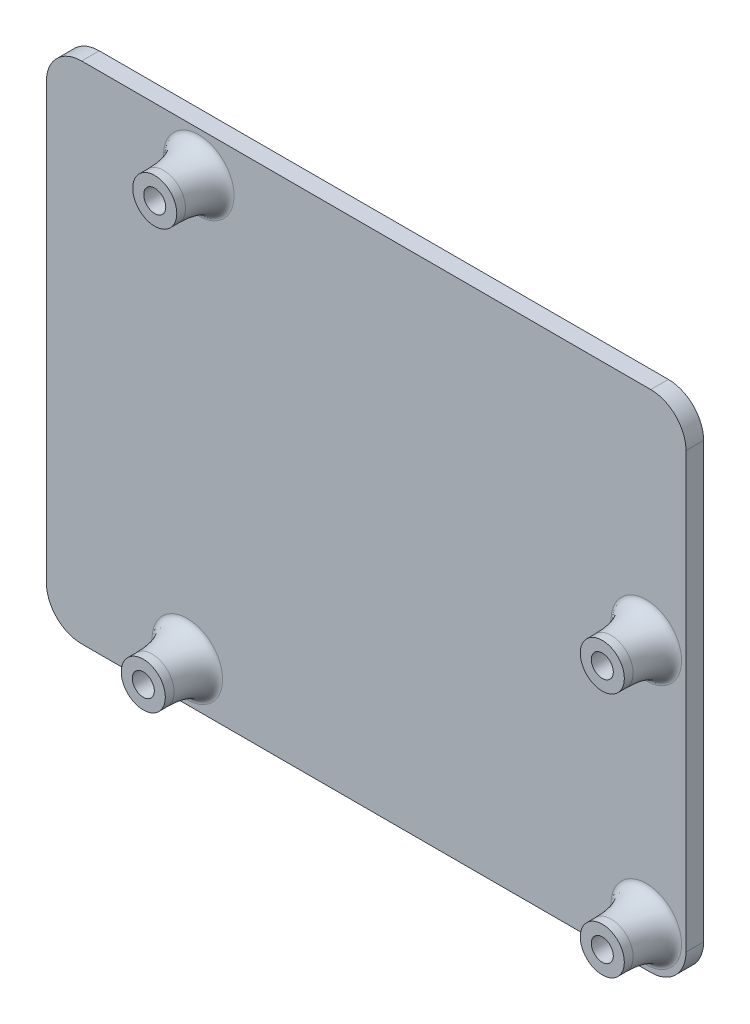
SolidWorks part; units mm, degrees
ref_plane "Front Plane" through (0, 0, 0) normal (0, 0, 1) x (1, 0, 0)
ref_plane "Top Plane" through (0, 0, 0) normal (0, 1, 0) x (1, 0, 0)
ref_plane "Right Plane" through (0, 0, 0) normal (1, 0, 0) x (0, 0, -1)
sketch "Sketch1" plane through (0, 0, 0) normal (0, 0, 1) x (1, 0, 0)
  line L1 (-17.3929, 25.8106) -> (51.2071, 25.8106)
  line L2 (-17.3929, 25.8106) -> (-17.3929, -27.4894)
  line L3 (-17.3929, -27.4894) -> (51.2071, -27.4894)
  line L4 (51.2071, 25.8106) -> (51.2071, -27.4894)
  dimension "D1" = 68.6
  dimension "D2" = 53.3
extrude "Boss-Extrude1" add sketch "Sketch1" along normal blind 2
sketch "Sketch2" plane through (0, 0, 2) normal (0, 0, 1) x (1, 0, 0)
  line L3 (-17.3929, -27.4894) -> (51.2071, -27.4894) construction
  line L4 (-17.3929, 25.8106) -> (-17.3929, -27.4894) construction
  point P5 (-2.0929, 23.2106)
  point P10 (48.7071, -24.9894)
  point P11 (-3.3929, -24.9894)
  point P12 (48.7071, 2.9106)
  dimension "D1" = 50.7
  dimension "D2" = 15.3
  dimension "D3" = 50.8
  dimension "D4" = 14
  dimension "D5" = 27.9
  dimension "D6" = 2.5
  dimension "D7" = 2.5
sketch "Sketch6" plane through (0, 0, 2) normal (0, 0, 1) x (1, 0, 0)
  line L8 (-19.3929, 27.8106) -> (-19.3929, -29.4894)
  line L9 (-19.3929, -29.4894) -> (53.2071, -29.4894)
  line L10 (53.2071, -29.4894) -> (53.2071, 27.8106)
  line L11 (53.2071, 27.8106) -> (-19.3929, 27.8106)
  line L12 (-19.3929, 27.8106) -> (-19.3929, -29.4894)
  line L13 (-19.3929, -29.4894) -> (53.2071, -29.4894)
  line L14 (53.2071, -29.4894) -> (53.2071, 27.8106)
  line L16 (53.2071, 27.8106) -> (-19.3929, 27.8106)
  dimension "D1" = 2
extrude "Boss-Extrude3" add sketch "Sketch6" against normal up to surface (2 mm away) up to face at (16.9071, -0.8394, 0)
sketch "Sketch3" plane through (0, 0, 2) normal (0, 0, 1) x (1, 0, 0)
  circle A0 centre (-2.0929, 23.2106) radius 2.5
  dimension "D1" = 5
  dimension "D2" = 0
  dimension "D3" = 0
extrude "Boss-Extrude2" add sketch "Sketch3" along normal blind 5
hole_wizard "Tap Drill for M3x0.5 Tap1" positions "Sketch4" profile "Sketch5" hole size "M3x0.5" standard "ANSI Metric"
sketch "Sketch4" plane through (0, 0, 7) normal (0, 0, 1) x (1, 0, 0)
  point P4 (-2.0929, 23.2106)
  point P14 (0, 0)
sketch "Sketch5" plane through (-2.0929, 23.2106, 7) normal (1, 0, 0) x (0, -1, 0)
  line L0 (0, 0) -> (0, 10.7511)
  line L1 (0, 10.7511) -> (1.25, 10)
  line L2 (1.25, 10) -> (1.25, 0)
  line L5 (1.25, 0) -> (0, 0)
  line L10 (0, 10.7511) -> (-1.25, 10) construction
  line L11 (0, -6.35) -> (0, 107.95) construction
  dimension "Hole Dia." = 2.5
  dimension "Hole Depth" = 10
  dimension "Drill Angle" = 118
pattern_sketch "Sketch-Pattern1" of "Boss-Extrude2", "Tap Drill for M3x0.5 Tap1" driven by "Sketch2"
fillet "Fillet1" radius 1.5 1 edges at (0.4071, 23.2106, 2)
fillet "Fillet2" radius 4 4 edges at (-19.3929, 27.8106, 1) (53.2071, 27.8106, 1) (53.2071, -29.4894, 1) (-19.3929, -29.4894, 1)
equation "\"D1@Sketch2\"=2.5+5.1+27.9+15.2"
